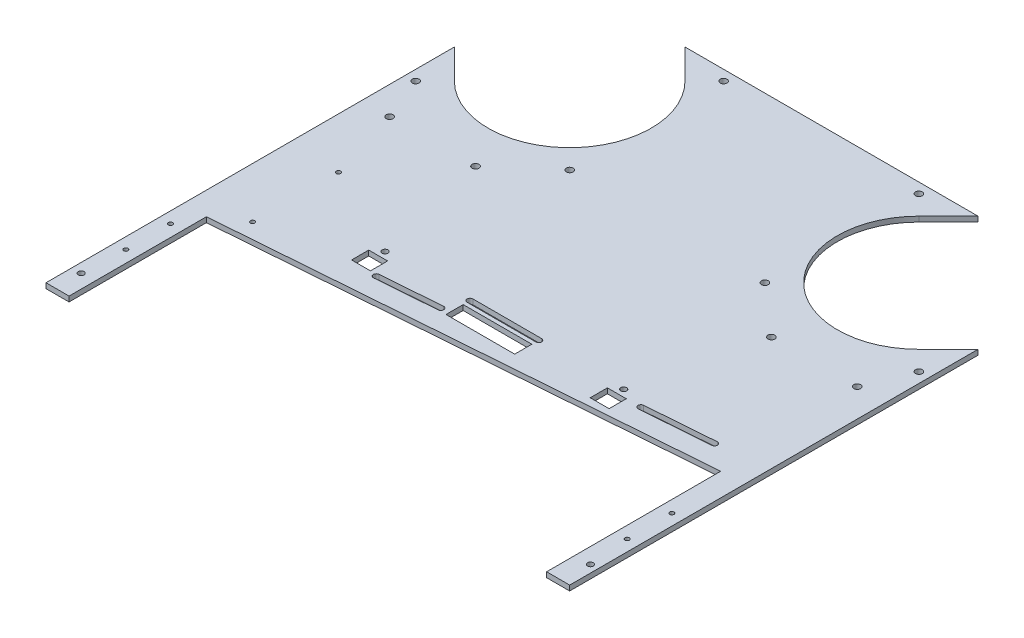
SolidWorks part; units mm, degrees
material "6061 Alloy"
ref_plane "Front Plane" through (0, 0, 0) normal (0, 0, 1) x (1, 0, 0)
ref_plane "Top Plane" through (0, 0, 0) normal (0, 1, 0) x (1, 0, 0)
ref_plane "Right Plane" through (0, 0, 0) normal (1, 0, 0) x (0, 0, -1)
sketch "Sketch1" plane through (0, 0, 0) normal (0, 1, 0) x (1, 0, 0)
  line L0 (0, 0) -> (0, 200)
  line L1 (0, 200) -> (305, 200)
  line L2 (305, 200) -> (305, 35.3098)
  line L3 (291.5711, -3.6044) -> (13.4289, -25)
  line L4 (0, 0) -> (0, -105)
  line L5 (0, -105) -> (13.4289, -105)
  line L6 (13.4289, -105) -> (13.4289, -25)
  line L7 (305, 35.3098) -> (305, -105)
  line L8 (305, -105) -> (291.5711, -105)
  line L9 (291.5711, -105) -> (291.5711, -3.6044)
  dimension "D1" = 305
  dimension "D2" = 85.601
  dimension "D3" = 200
  dimension "D4" = 13.4289
  dimension "D5" = 13.4289
  dimension "D6" = 105
  dimension "D7" = 305
  dimension "D8" = 80
sheet metal parameters "Sheet-Metal1" thickness 3 parameters "D1"=0.7366
base flange "Base-Flange1" sketch "Sketch1" thickness 3 reverse thickness direction no parameters "D1"=0.7366
hole_wizard "M3 Tapped Hole1" positions "Sketch6" profile "Sketch5" tap size "M3" standard "ISO"
sketch "Sketch6" plane through (0, 0, 0) normal (0, 1, 0) x (1, 0, 0)
  line L0 (0, 200) -> (0, -105) construction
  line L1 (305, -105) -> (305, 200) construction
  line L2 (0, -105) -> (13.4289, -105) construction
  line L3 (291.5711, -105) -> (305, -105) construction
  point P0 (6.5, -39)
  point P2 (6.5, -65)
  point P4 (298.5, -39)
  point P6 (298.5, -65)
  dimension "D1" = 6.5
  dimension "D3" = 6.5
  dimension "D5" = 26
  dimension "D6" = 26
  dimension "D7" = 40
  dimension "D8" = 40
sketch "Sketch5" plane through (6.5, 0, 39) normal (1, 0, 0) x (0, 0, 1)
  line L0 (0, 0) -> (0, 8.2511)
  line L1 (0, 8.2511) -> (1.25, 7.5)
  line L2 (1.25, 7.5) -> (1.25, 0)
  line L5 (1.25, 0) -> (0, 0)
  line L10 (0, 8.2511) -> (-1.25, 7.5) construction
  line L11 (0, -6.35) -> (0, 107.95) construction
  dimension "Tap Drill Dia." = 2.5
  dimension "Tap Drill Depth" = 7.5
  dimension "Drill Angle" = 118
cosmetic thread "Hole Thread1" parameters "D1"=3, "D2"=3
cosmetic thread "Hole Thread2" parameters "D1"=3, "D2"=3
cosmetic thread "Hole Thread3" parameters "D1"=3, "D2"=3
cosmetic thread "Hole Thread4" parameters "D1"=3, "D2"=3
sketch "Sketch11" plane through (0, 0, 0) normal (0, 1, 0) x (1, 0, 0)
  line L0 (0, 132.8249) -> (17.2124, 115.6124)
  line L1 (0, 200) -> (0, -105) construction
  line L2 (17.2124, 115.6124) -> (0, 115.6124) construction
  line L3 (84.3876, 182.7876) -> (67.1751, 200)
  line L4 (305, 200) -> (0, 200) construction
  line L5 (220.6124, 182.7876) -> (237.8249, 200)
  line L6 (287.7876, 115.6124) -> (305, 132.8249)
  line L7 (305, -105) -> (305, 200) construction
  line L8 (287.7876, 115.6124) -> (305, 115.6124) construction
  line L9 (0, 132.8249) -> (0, 200)
  line L10 (0, 200) -> (67.1751, 200)
  circle A0 centre (50.8, 149.2) radius 47.5
  circle A1 centre (254.2, 149.2) radius 47.5
  circle A2 centre (95.6437, 194.0437) radius 1.9844
  circle A3 centre (5.9563, 104.3563) radius 1.9844
  circle A4 centre (95.6437, 104.3563) radius 1.9844
  circle A5 centre (209.3563, 104.3563) radius 1.9844
  circle A6 centre (299.0437, 104.3563) radius 1.9844
  circle A7 centre (209.3563, 194.0437) radius 1.9844
  circle A8 centre (66.3384, 78.8315) radius 2
  circle A9 centre (16.3384, 78.8315) radius 2
  circle A10 centre (288.6616, 78.8319) radius 2
  circle A11 centre (238.6616, 78.8319) radius 2
  line M10 (0, 200) -> (0, -105)
  line M16 (305, -105) -> (305, 200)
  line M17 (305, 200) -> (0, 200)
  dimension "D2" = 95
  dimension "D3" = 95
  dimension "D8" = 3.9688
  dimension "D9" = 3.9688
  dimension "D11" = 3.9688
  dimension "D15" = 3.9687
  dimension "D16" = 3.9687
  dimension "D19" = 3.9687
  dimension "D18" = 4
  dimension "D20" = 4
  dimension "D21" = 4
  dimension "D22" = 4
  dimension "D1" = 45
  dimension "D4" = 45
  dimension "D5" = 5.9563
  dimension "D6" = 89.6874
  dimension "D7" = 95.6437
  dimension "D10" = 5.9563
  dimension "D12" = 5.9563
  dimension "D13" = 95.6437
  dimension "D14" = 95.6437
  dimension "D17" = 5.9563
extrude "Cut-Extrude1" cut sketch "Sketch11" against normal through all contours A0 L3 L0 M17 M10 | A0 | A1 | A1 L6 L5 M16 M17 | A2 | A3 | A4 | A7 | A5 | A6 | A9 | A8 | A11 | A10 region at (1.1934, 0, -166.4124) region at (271.4124, 0, -198.8066) region at (50.8, 0, -149.2) region at (254.2, 0, -149.2) region at (95.6437, 0, -194.0437) region at (5.9563, 0, -104.3563) region at (95.6437, 0, -104.3563) region at (209.3563, 0, -104.3563) region at (299.0437, 0, -104.3563) region at (209.3563, 0, -194.0437) region at (66.3384, 0, -78.8315) region at (16.3384, 0, -78.8315) region at (288.6616, 0, -78.8319) region at (238.6616, 0, -78.8319) normal cut yes
hole_wizard "M3 Tapped Hole3" positions "Sketch13" profile "Sketch12" tap size "M3" standard "ISO"
sketch "Sketch13" plane through (0, 0, 0) normal (0, 1, 0) x (1, 0, 0)
  point P0 (29.4743, 35.8573)
  point P3 (29.4743, -14.1427)
sketch "Sketch12" plane through (29.4743, 0, -35.8573) normal (1, 0, 0) x (0, 0, 1)
  line L0 (0, 0) -> (0, 8.2511)
  line L1 (0, 8.2511) -> (1.25, 7.5)
  line L2 (1.25, 7.5) -> (1.25, 0)
  line L5 (1.25, 0) -> (0, 0)
  line L10 (0, 8.2511) -> (-1.25, 7.5) construction
  line L11 (0, -6.35) -> (0, 107.95) construction
  dimension "Tap Drill Dia." = 2.5
  dimension "Tap Drill Depth" = 7.5
  dimension "Drill Angle" = 118
cosmetic thread "Hole Thread7" parameters "D1"=3, "D2"=3
cosmetic thread "Hole Thread8" parameters "D1"=3, "D2"=3
sketch "Sketch14" plane through (0, 0, 0) normal (0, 1, 0) x (1, 0, 0)
  line L0 (152.5, 200) -> (152.5, -163.8054) construction
  line L1 (237.8249, 200) -> (67.1751, 200) construction
  line L3 (77.5, -4.533) -> (227.5, -4.533)
  line L4 (77.5, -4.533) -> (77.5, 5.467)
  line L5 (77.5, 5.467) -> (227.5, 5.467)
  line L6 (227.5, -4.533) -> (227.5, 5.467)
  line L11 (77.5, -4.533) -> (227.5, 5.467) construction
  line L12 (77.5, 5.467) -> (227.5, -4.533) construction
  line L13 (88.5, 5.467) -> (88.5, -4.533)
  line L14 (216.5, 5.467) -> (216.5, -4.533)
  line L15 (132.5, 5.467) -> (132.5, -4.533)
  line L16 (172.5, 5.467) -> (172.5, -4.533)
  line L21 (13.4289, -25) -> (291.5711, -3.6044) construction
  line L22 (227.5, -4.533) -> (227.5, -8.533) construction
  point P4 (152.5, 0.467)
  dimension "D1" = 150
  dimension "D2" = 10
  dimension "D3" = 11
  dimension "D4" = 11
  dimension "D5" = 20
  dimension "D6" = 20
  dimension "D7" = 4
extrude "QRD Slots" cut sketch "Sketch14" against normal blind 10 contours L5 L14 L3 L6 | L16 L5 L15 L3 | L13 L5 L4 L3 region at (83, 0, -0.467) region at (152.5, 0, -0.467) region at (222, 0, -0.467) normal cut yes
sketch "Sketch15" plane through (0, 0, 0) normal (0, 1, 0) x (1, 0, 0)
  line L0 (275.8299, 8.5925) -> (92.848, -5.483) construction
  line L1 (275.9603, 6.8975) -> (92.9784, -7.178)
  line L2 (275.6995, 10.2875) -> (92.7176, -3.788)
  arc A0 (275.9603, 6.8975) -> (275.6995, 10.2875) centre (275.8299, 8.5925) ccw
  arc A1 (92.7176, -3.788) -> (92.9784, -7.178) centre (92.848, -5.483) ccw
  arc A2 (235.8173, 7.2196) -> (236.0781, 3.8296) centre (235.9477, 5.5246) ccw
  arc A5 (127.8753, -4.4937) -> (127.6145, -1.1037) centre (127.7449, -2.7987) ccw
  point P3 (184.339, 1.5547)
  dimension "D1" = 1.7
  dimension "D2" = 35
  dimension "D3" = 40
extrude "Wall Mounting Slots" cut sketch "Sketch15" against normal blind 10 contours L1 A5 L2 A1 | A2 L1 A0 L2 region at (255.8888, 0, -7.0586) region at (110.2965, 0, 4.1409) normal cut yes
hole_wizard "M3 Clearance Hole1" positions "Sketch17" profile "Sketch18" hole size "M3" standard "ISO"
sketch "Sketch17" plane through (0, 0, 0) normal (0, 1, 0) x (1, 0, 0)
  line L0 (77.5, 5.467) -> (88.5, 5.467) construction
  line L1 (216.5, 5.467) -> (227.5, 5.467) construction
  line L2 (222, 5.467) -> (222, 9.467) construction
  line L4 (83, 9.467) -> (83, 5.467) construction
  point P0 (83, 9.467)
  point P3 (222, 9.467)
  dimension "D1" = 4
  dimension "D2" = 4
sketch "Sketch18" plane through (83, 0, -9.467) normal (1, 0, 0) x (0, 0, 1)
  line L0 (0, 0) -> (0, 11.0215)
  line L1 (0, 11.0215) -> (1.7, 10)
  line L2 (1.7, 10) -> (1.7, 0)
  line L5 (1.7, 0) -> (0, 0)
  line L10 (0, 11.0215) -> (-1.7, 10) construction
  line L11 (0, -6.35) -> (0, 107.95) construction
  dimension "Hole Dia." = 3.4
  dimension "Hole Depth" = 10
  dimension "Drill Angle" = 118
sketch "Sketch19" plane through (0, 0, 0) normal (0, 1, 0) x (1, 0, 0)
  line L0 (132.5, 9.467) -> (172.5, 9.467) construction
  line L1 (132.5, 11.167) -> (172.5, 11.167)
  line L2 (132.5, 7.767) -> (172.5, 7.767)
  line L3 (132.5, 5.467) -> (172.5, 5.467) construction
  line L5 (132.5, 9.467) -> (132.5, 5.467) construction
  line L6 (172.5, 9.467) -> (172.5, 5.467) construction
  line L7 (132.5, 5.467) -> (132.5, -4.533) construction
  line L8 (172.5, 5.467) -> (172.5, -4.533) construction
  arc A0 (132.5, 11.167) -> (132.5, 7.767) centre (132.5, 9.467) ccw
  arc A1 (172.5, 7.767) -> (172.5, 11.167) centre (172.5, 9.467) ccw
  point P2 (152.5, 9.467)
  dimension "D1" = 1.7
  dimension "D2" = 4
extrude "Cut-Extrude2" cut sketch "Sketch19" against normal through all normal cut yes
sketch "Sketch20" plane through (0, 0, 0) normal (0, 1, 0) x (1, 0, 0)
  circle A0 centre (300.6041, -88.525) radius 1.7
  circle A1 centre (5.4289, -90) radius 1.7
extrude "Cut-Extrude3" cut sketch "Sketch20" against normal through all normal cut yes
flat pattern "Flat-Pattern1" [suppressed]
sketch "Bend-Lines1" plane through (0, 0, 0) normal (0, 1, 0) x (1, 0, 0)
sketch3d "Bounding-Box1" [suppressed]
  line L0 (-304.8, 200, 0) -> (0, 200, 0) construction
  line L1 (-304.8, 0, 0) -> (0, 0, 0) construction
  line L2 (-304.8, 200, 0) -> (-304.8, 0, 0) construction
  line L3 (0, 200, 0) -> (0, 0, 0) construction
equation "\"D5@Sketch1\"=\"D4@Sketch1\""
equation "\"D6@Sketch14\"=\"D5@Sketch14\""
